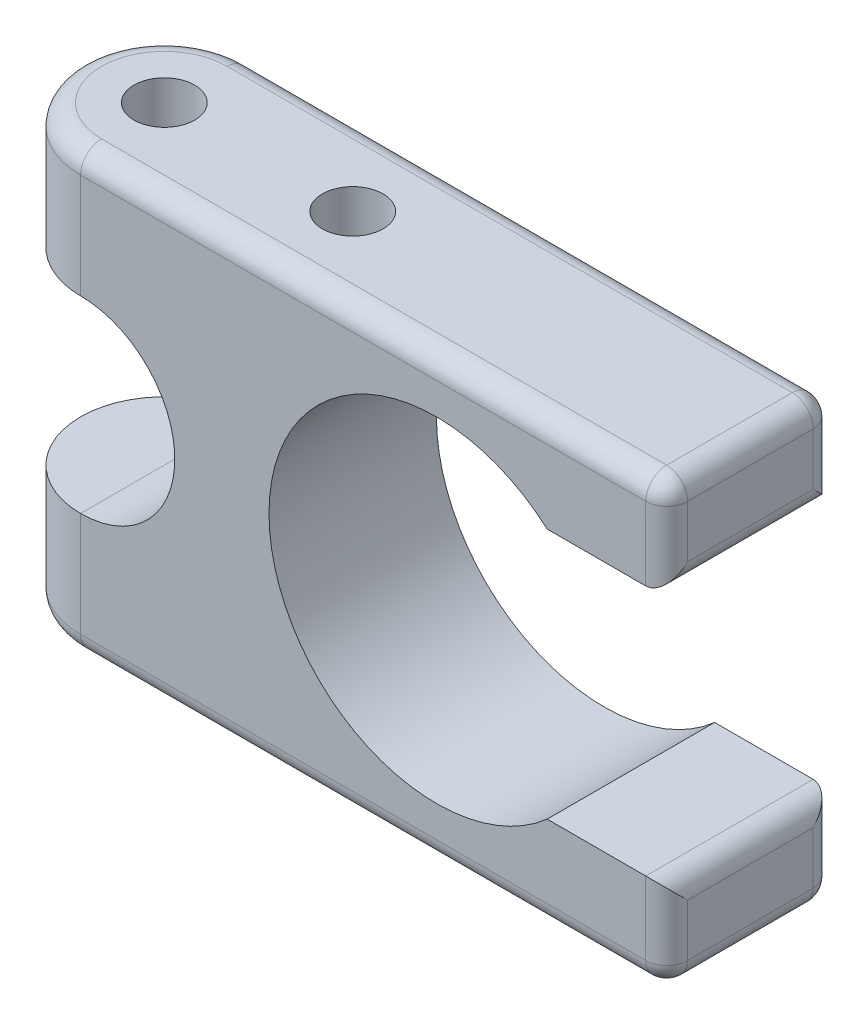
SolidWorks part; units mm, degrees
material "ABS"
ref_plane "Front Plane" through (0, 0, 0) normal (0, 0, 1) x (1, 0, 0)
ref_plane "Top Plane" through (0, 0, 0) normal (0, 1, 0) x (1, 0, 0)
ref_plane "Right Plane" through (0, 0, 0) normal (1, 0, 0) x (0, 0, -1)
sketch "Sketch1" plane through (0, 0, 0) normal (0, 0, 1) x (1, 0, 0)
  line L1 (16, 10.5) -> (-16, 10.5)
  line L2 (16, 10.5) -> (16, -10.5)
  line L3 (16, -10.5) -> (-16, -10.5)
  line L4 (-16, 10.5) -> (-16, -10.5)
  line L5 (16, 10.5) -> (-16, -10.5) construction
  line L6 (16, -10.5) -> (-16, 10.5) construction
  point P0 (0, 0)
  dimension "D1" = 21
  dimension "D2" = 32
extrude "Boss-Extrude1" add sketch "Sketch1" along normal blind 8
fillet "Fillet1" 2 edges at (-16, 0, 8) (-16, 0, 0) type full round first side face at (0, 0, 8) second side face at (0, 0, 0) middle face at (-16, 0, 4)
sketch "Sketch2" plane through (0, 0, 8) normal (0, 0, 1) x (1, 0, 0)
  line L0 (-16, 10.5) -> (-16, -10.5) construction
  line L1 (16, 6) -> (10.2915, 6)
  line L2 (16, -10.5) -> (16, 10.5) construction
  line L3 (16, -6) -> (10.2915, -6)
  line L4 (16, -6) -> (16, 6)
  arc A0 (10.2915, 6) -> (10.2915, -6) centre (5, 0) ccw
  dimension "D1" = 16
  dimension "D2" = 21
  dimension "D3" = 12
extrude "Cut-Extrude1" cut sketch "Sketch2" against normal up to next
hole_wizard "M2.5 Clearance Hole1" positions "Sketch3" profile "Sketch5" hole size "M2.5" standard "ANSI Metric"
sketch "Sketch3" plane through (0, 10.5, 0) normal (0, 1, 0) x (1, 0, 0)
  line L0 (-12, -4) -> (-3, -4) construction
  point P0 (-12, -4)
  point P3 (-3, -4)
  dimension "D1" = 9
sketch "Sketch5" plane through (-12, 10.5, 4) normal (1, 0, 0) x (0, 0, 1)
  line L0 (0, 0) -> (0, 4.8712)
  line L1 (0, 4.8712) -> (1.45, 4)
  line L2 (1.45, 4) -> (1.45, 0)
  line L5 (1.45, 0) -> (0, 0)
  line L10 (0, 4.8712) -> (-1.45, 4) construction
  line L11 (0, -6.35) -> (0, 107.95) construction
  dimension "Hole Dia." = 2.9
  dimension "Hole Depth" = 4
  dimension "Drill Angle" = 118
fillet "Fillet2" radius 1 14 edges at (2, -10.5, 0) (-16, -10.5, 4) (2, 10.5, 0) (2, 10.5, 8) (16, -8.25, 0) (16, -8.25, 8) (16, -6, 4) (16, 6, 4) (16, 8.25, 0) (16, 8.25, 8) (16, 10.5, 4) (16, -10.5, 4) (2, -10.5, 8) (-16, 10.5, 4)
mirror "Mirror1" about plane through (0, 0, 0) normal (0, 1, 0) of "M2.5 Clearance Hole1"
sketch "Sketch6" plane through (0, 0, 0) normal (0, 0, 1) x (1, 0, 0)
  line L0 (-12, 9.5) -> (-12, -9.5) construction
  line L1 (-12, 4.5) -> (-16, 4.5)
  line L2 (-16, 9.5) -> (-16, -9.5) construction
  line L3 (-12, -4.5) -> (-16, -4.5)
  line L4 (-16, 4.5) -> (-16, -4.5)
  line L5 (-12, 0) -> (0, 0) construction
  arc A0 (-12, -4.5) -> (-12, 4.5) centre (-12, 0) ccw
  dimension "D1" = 9
extrude "Cut-Extrude2" cut sketch "Sketch6" along normal up to next
